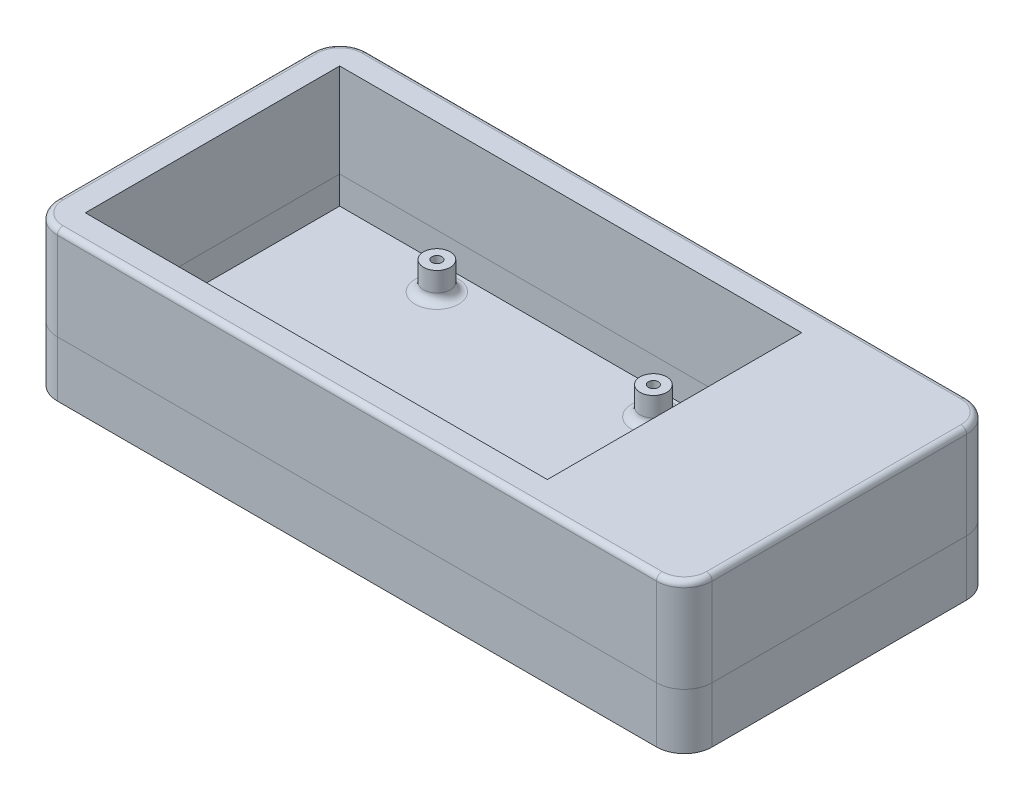
SolidWorks part; units mm, degrees
ref_plane "Front Plane" through (0, 0, 0) normal (0, 0, 1) x (1, 0, 0)
ref_plane "Top Plane" through (0, 0, 0) normal (0, 1, 0) x (1, 0, 0)
ref_plane "Right Plane" through (0, 0, 0) normal (1, 0, 0) x (0, 0, -1)
sketch "Sketch1" plane through (0, 0, 0) normal (0, 1, 0) x (1, 0, 0)
  line L1 (-44.3337, 20.1048) -> (63.2663, 20.1048)
  line L2 (-44.3337, 20.1048) -> (-44.3337, -25.5852)
  line L3 (-44.3337, -25.5852) -> (63.2663, -25.5852)
  line L4 (63.2663, 20.1048) -> (63.2663, -25.5852)
  line L5 (-44.3337, 20.1048) -> (63.2663, 20.1048)
  line L7 (-44.3337, 25.1048) -> (63.2663, 25.1048)
  line L10 (-44.3337, 20.1048) -> (-44.3337, -25.5852)
  line L12 (-49.3337, 20.1048) -> (-49.3337, -25.5852)
  line L14 (63.2663, 20.1048) -> (63.2663, -25.5852)
  line L16 (68.2663, 20.1048) -> (68.2663, -25.5852)
  line L17 (-44.3337, -25.5852) -> (63.2663, -25.5852)
  line L19 (-44.3337, -30.5852) -> (63.2663, -30.5852)
  arc A0 (-49.3337, 20.1048) -> (-44.3337, 25.1048) centre (-44.3337, 20.1048) cw
  arc A2 (68.2663, -25.5852) -> (63.2663, -30.5852) centre (63.2663, -25.5852) cw
  arc A3 (-44.3337, -30.5852) -> (-49.3337, -25.5852) centre (-44.3337, -25.5852) cw
  arc A4 (63.2663, 25.1048) -> (68.2663, 20.1048) centre (63.2663, 20.1048) cw
  dimension "D1" = 107.6
  dimension "D2" = 45.69
  dimension "D3" = 5
  dimension "D4" = 5
  dimension "D5" = 5
  dimension "D6" = 5
  dimension "D7" = 45.69
  dimension "D8" = 107.6
  dimension "D9" = 107.6
extrude "Boss-Extrude2" add sketch "Sketch1" along normal blind 26.8 contours L12 A3 L19 A2 L16 A4 L7 A0
sketch "Sketch2" plane through (0, 26.8, 0) normal (0, 1, 0) x (1, 0, 0)
  line L1 (-44.3337, 20.1048) -> (63.2663, 20.1048)
  line L2 (-44.3337, 20.1048) -> (-44.3337, -25.5852)
  line L3 (-44.3337, -25.5852) -> (63.2663, -25.5852)
  line L4 (63.2663, 20.1048) -> (63.2663, -25.5852)
extrude "Cut-Extrude2" cut sketch "Sketch2" against normal blind 21.8
sketch "Sketch3" plane through (0, 5, 0) normal (0, 1, 0) x (1, 0, 0)
  line L0 (-44.3337, 20.1048) -> (-44.3337, -25.5852) construction
  line L1 (63.2663, 20.1048) -> (-44.3337, 20.1048) construction
  line L2 (63.2663, 20.1048) -> (-44.3337, 20.1048) construction
  circle A0 centre (-22.2837, 15.5148) radius 0.9
  circle A2 centre (16.6063, 15.5148) radius 0.9
  circle A3 centre (-2.4437, -20.9952) radius 0.9
  circle A4 centre (-22.2837, 15.5148) radius 2.4
  circle A5 centre (16.6063, 15.5148) radius 2.4
  circle A6 centre (-2.4437, -20.9952) radius 2.4
  dimension "D1" = 22.05
  dimension "D3" = 4.59
  dimension "D5" = 19.84
  dimension "D2" = 4.59
  dimension "D4" = 38.89
  dimension "D6" = 36.51
extrude "Boss-Extrude3" add sketch "Sketch3" along normal blind 5 contours A4 | A0 | A5 | A2 | A6 | A3
fillet "Fillet3" radius 1 8 edges at (-47.8693, 26.8, 29.1207) (-47.8693, 26.8, -23.6404) (66.8018, 26.8, -23.6404) (66.8018, 26.8, 29.1207) (9.4663, 26.8, -25.1048) (-49.3337, 26.8, 2.7402) (68.2663, 26.8, 2.7402) (9.4663, 26.8, 30.5852)
fillet "Fillet5" radius 1.5 1 edges at (16.6063, 5, -13.1148)
fillet "Fillet6" radius 1.5 1 edges at (-22.2837, 5, -13.1148)
fillet "Fillet7" radius 1.5 1 edges at (-2.4437, 5, 23.3952)
ref_plane "Plane1" through (0, 0, -20.1048) normal (0, 0, 1) x (1, 0, 0)
sketch "Sketch10" plane through (0, 0, -20.1048) normal (0, 0, 1) x (1, 0, 0)
  line L1 (63.2663, 26.8) -> (38.6563, 26.8)
  line L2 (63.2663, 26.8) -> (63.2663, 21.8)
  line L3 (63.2663, 21.8) -> (38.6563, 21.8)
  line L4 (38.6563, 26.8) -> (38.6563, 21.8)
  dimension "D1" = 24.61
  dimension "D2" = 5
extrude "Boss-Extrude4" add sketch "Sketch10" along normal up to next contours L2 L1 L4 L3
sketch "Sketch13" plane through (0, 0, -20.1048) normal (0, 0, 1) x (1, 0, 0)
  line L0 (68.2663, 25.8) -> (68.2663, 0) construction
  line L1 (42.1263, 11) -> (52.6263, 11)
  line L2 (41.6263, 10.5) -> (41.6263, 7.2)
  line L3 (42.1263, 6.7) -> (52.6263, 6.7)
  line L4 (53.1263, 10.5) -> (53.1263, 7.2)
  line L6 (-44.3337, 0) -> (63.2663, 0) construction
  arc A0 (41.6263, 7.2) -> (42.1263, 6.7) centre (42.1263, 7.2) ccw
  arc A1 (52.6263, 6.7) -> (53.1263, 7.2) centre (52.6263, 7.2) ccw
  arc A2 (53.1263, 10.5) -> (52.6263, 11) centre (52.6263, 10.5) ccw
  arc A3 (41.6263, 10.5) -> (42.1263, 11) centre (42.1263, 10.5) cw
  point P10 (41.6263, 6.7)
  point P13 (53.1263, 6.7)
  point P16 (53.1263, 11)
  dimension "D5" = 0.5
  dimension "D1" = 11.5
  dimension "D2" = 4.3
  dimension "D3" = 15.14
  dimension "D4" = 11
extrude "Cut-Extrude3" cut sketch "Sketch13" against normal blind 5
sketch "Sketch14" plane through (0, 0, -20.1048) normal (0, 0, 1) x (1, 0, 0)
  line L0 (-49.3337, 10) -> (68.2663, 10)
  line L1 (-49.3337, 25.8) -> (-49.3337, 0) construction
  line L2 (68.2663, 25.8) -> (68.2663, 0) construction
  line L3 (63.2663, 0) -> (68.2663, 0) construction
  dimension "D1" = 10
split "Split1" trim tools "Sketch14" bodies to split 107 resulting bodies 110 111
